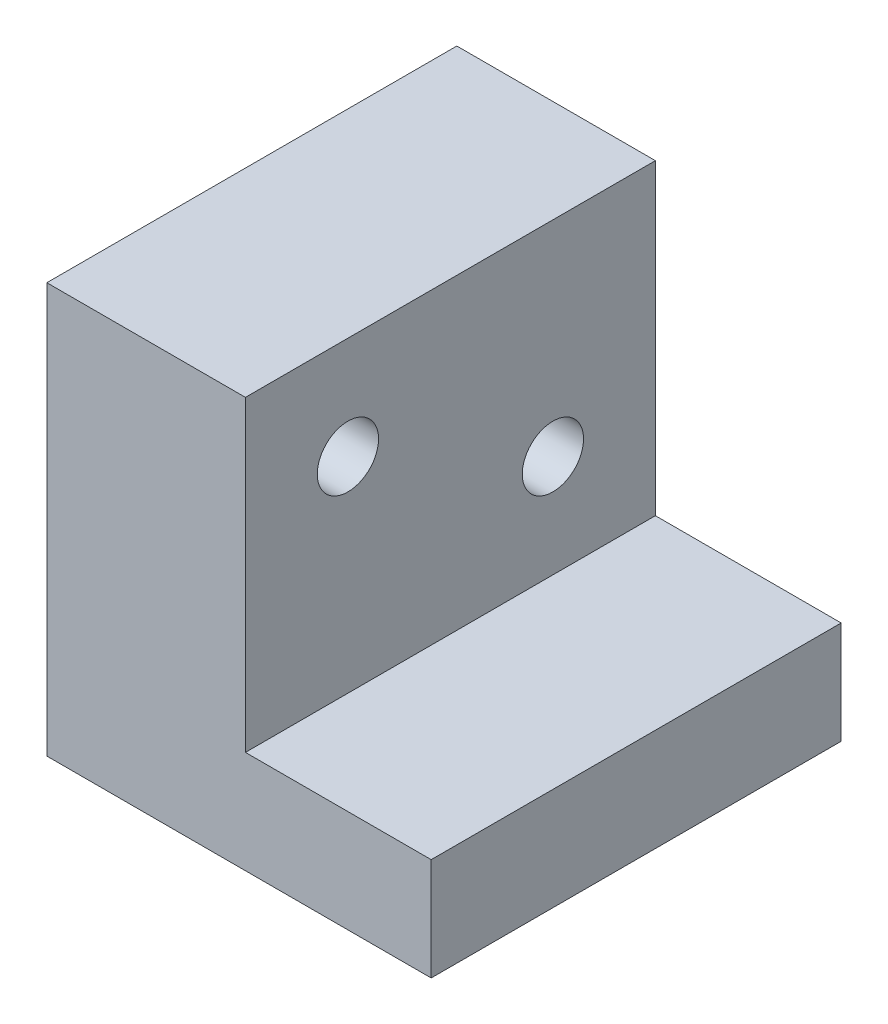
SolidWorks part; units mm, degrees
material "DELRIN (WHITE)"
ref_plane "Front" through (0, 0, 0) normal (0, 0, 1) x (1, 0, 0)
ref_plane "Top" through (0, 0, 0) normal (0, 1, 0) x (1, 0, 0)
ref_plane "Right" through (0, 0, 0) normal (1, 0, 0) x (0, 0, -1)
ref_axis "Axis1" through (0, 50, 0) along (0, -1, 0)
sketch "Sketch1" plane through (0, 0, 0) normal (1, 0, 0) x (0, 0, -1)
  line L1 (-12.7, 12.7) -> (12.7, 12.7)
  line L2 (-12.7, 12.7) -> (-12.7, -12.7)
  line L3 (-12.7, -12.7) -> (12.7, -12.7)
  line L4 (12.7, 12.7) -> (12.7, -12.7)
  line L5 (-12.7, 12.7) -> (12.7, -12.7) construction
  line L6 (-12.7, -12.7) -> (12.7, 12.7) construction
  point P0 (0, 0)
  dimension "D1" = 25.4
  dimension "D2" = 25.4
extrude "Extrude1" add sketch "Sketch1" against normal blind 23.8125
sketch "Sketch2" plane through (0, 0, 12.7) normal (0, 0, 1) x (1, 0, 0)
  line L1 (-11.5094, 12.7) -> (0, 12.7)
  line L2 (-11.5094, 12.7) -> (-11.5094, -6.35)
  line L3 (-11.5094, -6.35) -> (0, -6.35)
  line L4 (0, 12.7) -> (0, -6.35)
  line L5 (-23.8125, -12.7) -> (0, -12.7) construction
  line L6 (-23.8125, 12.7) -> (0, 12.7) construction
  line L7 (0, 12.7) -> (0, -12.7) construction
  line L8 (-23.8125, 12.7) -> (-23.8125, -12.7) construction
  dimension "D1" = 12.3031
  dimension "D2" = 6.35
extrude "Extrude2" cut sketch "Sketch2" against normal through all
hole_wizard "#10-24 Tapped Hole1" positions "Sketch4" profile "Sketch3" tap size "#10-24" standard "Ansi Inch" end condition through all
sketch "Sketch4" plane through (0, 0, 0) normal (1, 0, 0) x (0, 0, -1)
  line L0 (-12.7, -12.7) -> (12.7, -12.7) construction
  line L1 (-12.7, -6.35) -> (-12.7, -12.7) construction
  point P0 (6.35, 0)
  point P1 (-6.35, 6.35)
  dimension "D1" = 12.7
  dimension "D2" = 12.7
  dimension "D3" = 6.35
  dimension "D4" = 6.35
sketch "Sketch3" plane through (0, 0, -6.35) normal (0, 1, 0) x (0, 0, -1)
  line L0 (0, 0) -> (0, 23.8125)
  line L1 (0, 23.8125) -> (1.8986, 23.8125)
  line L2 (1.8986, 23.8125) -> (1.8986, 0)
  line L5 (1.8986, 0) -> (0, 0)
  line L11 (0, -6.35) -> (0, 107.95) construction
  dimension "Thru Tap Drill Dia." = 3.7973
  dimension "Thru Tap Drill Depth" = 23.8125
cosmetic thread "Hole Thread1" parameters "D2"=4.826
cosmetic thread "Hole Thread2" parameters "D2"=4.826
